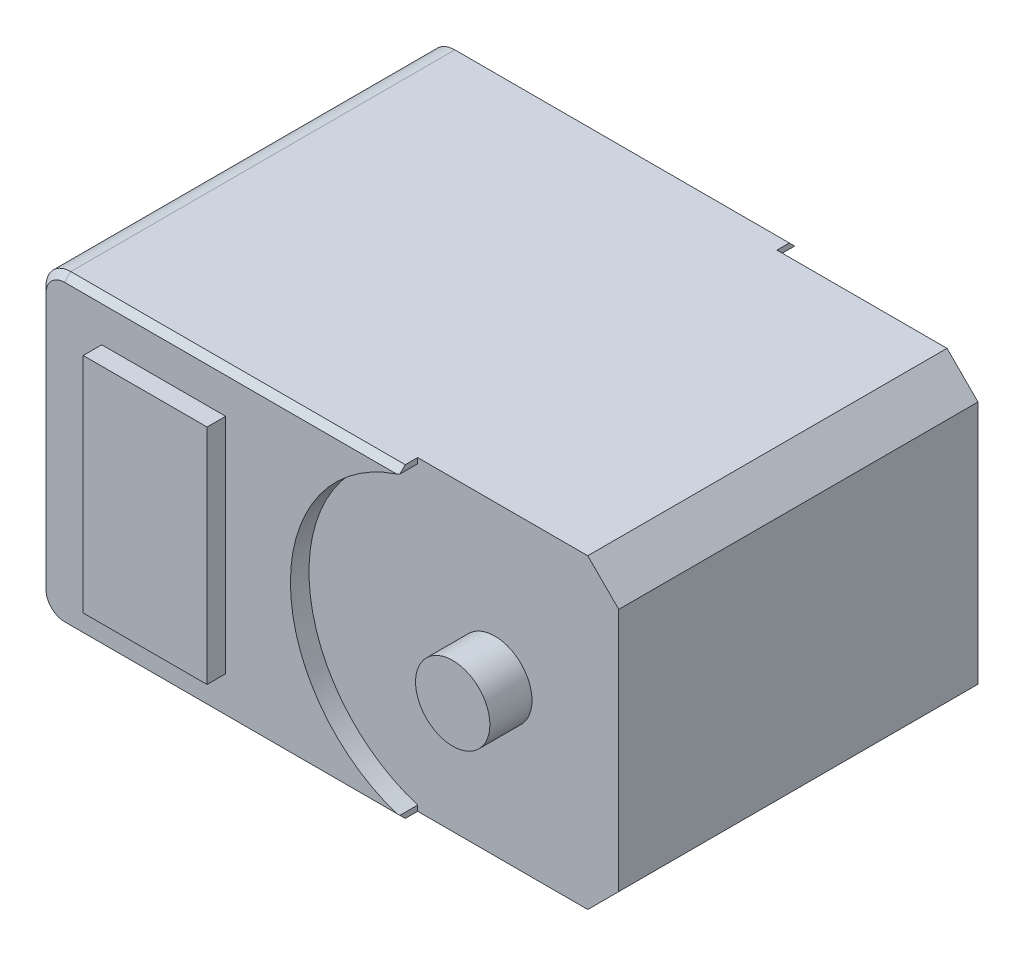
SolidWorks part; units mm, degrees
material "舵机材料"
ref_plane "前视基准面" through (0, 0, 0) normal (0, 0, 1) x (1, 0, 0)
ref_plane "上视基准面" through (0, 0, 0) normal (0, 1, 0) x (1, 0, 0)
ref_plane "右视基准面" through (0, 0, 0) normal (1, 0, 0) x (0, 0, -1)
other "Configuration Table"
sketch "草图1" plane through (0, 0, 0) normal (0, 0, 1) x (1, 0, 0)
  line L1 (0, 0) -> (45.23, 0)
  line L2 (0, 0) -> (0, 24.73)
  line L3 (0, 24.73) -> (45.23, 24.73)
  line L4 (45.23, 0) -> (45.23, 24.73)
  dimension "D1" = 45.23
  dimension "D2" = 24.73
extrude "凸台-拉伸1" add sketch "草图1" along normal blind 35
sketch "草图2" plane through (0, 0, 0) normal (0, 0, 1) x (1, 0, 0)
  line L1 (45.23, 24.73) -> (30.8978, 24.73)
  line L2 (45.23, 24.73) -> (45.23, 0)
  line L3 (45.23, 0) -> (30.8978, 0)
  line L9 (0, 24.73) -> (0, 0)
  line L10 (0, 0) -> (45.23, 0)
  line L11 (45.23, 0) -> (45.23, 24.73)
  line L12 (45.23, 24.73) -> (0, 24.73)
  line L14 (30.8978, 0) -> (45.23, 0)
  line L15 (45.23, 0) -> (45.23, 24.73)
  line L16 (45.23, 24.73) -> (30.8978, 24.73)
  arc A0 (30.8978, 24.73) -> (30.8978, 0) centre (32.73, 12.365) ccw
  dimension "D2" = 0
extrude "切除-拉伸1" cut sketch "草图2" along normal blind 3 contours L1 A0 L3 L2 region at (33.867, 12.365, 0)
sketch "草图5" plane through (0, 0, 0) normal (0, 0, 1) x (1, 0, 0)
  line L0 (30.8978, 24.73) -> (0, 24.73) construction
  line L2 (0, 0) -> (0, 24.73)
  line L4 (29, 0) -> (29, 24.73)
  line L5 (30.8978, 0) -> (30.8978, 24.73)
  line L14 (30.8978, 24.73) -> (0, 24.73)
  line L15 (0, 0) -> (30.8978, 0)
  line L16 (0, 24.73) -> (0, 0)
  line L17 (30.8978, 24.73) -> (29, 24.73)
  line L18 (29, 0) -> (30.8978, 0)
  line L19 (0, 24.73) -> (0, 0)
  arc A4 (30.8978, 24.73) -> (30.8978, 0) centre (32.73, 12.365) ccw
  dimension "D1" = 29
  dimension "D3" = 0
extrude "切除-拉伸3" cut sketch "草图5" along normal up to surface (3 mm away) contours L4 L18 L5 L17 region at (29.5901, 0.137, 0) region at (29.5901, 24.593, 0) region at (29.9546, 12.365, 0) up to face at (35.397, 12.365, 3)
ref_plane "基准面1" through (0, 0, 17.5) normal (0, 0, 1) x (1, 0, 0)
mirror "镜向1" about plane through (0, 0, 17.5) normal (0, 0, 1) of "切除-拉伸3", "切除-拉伸1"
sketch "草图3" plane through (0, 0, 0) normal (0, 0, 1) x (1, 0, 0)
  arc A0 (29, 24.2955) -> (29, 0.4345) centre (32.73, 12.365) ccw construction
  arc A1 (29, 24.2955) -> (29, 0.4345) centre (32.73, 12.365) ccw
  circle A3 centre (35.23, 12.365) radius 3
  dimension "D1" = 6
  dimension "D2" = 2.5
extrude "凸台-拉伸2" add sketch "草图3" along normal blind 17.9 and the other way blind 18.6 from surface contours A3 region at (35.23, 12.365, 0) starting at plane "基准面1"
sketch "草图4" plane through (0, 0, 0) normal (0, 0, 1) x (1, 0, 0)
  line L0 (0, 12.365) -> (51.1364, 12.365) construction
  line L1 (0, 24.73) -> (30.8978, 24.73)
  line L2 (0, 24.73) -> (0, 19.73)
  line L3 (0, 19.73) -> (30.8978, 19.73)
  line L4 (30.8978, 24.73) -> (30.8978, 19.73)
  line L5 (0, 24.73) -> (0, 0) construction
  line L6 (30.8978, 0) -> (30.8978, 5)
  line L7 (0, 0) -> (0, 5)
  line L8 (0, 0) -> (30.8978, 0)
  line L9 (0, 5) -> (30.8978, 5)
  dimension "D1" = 5
extrude "切除-拉伸2" cut sketch "草图4" along normal blind 1.5
chamfer "倒角1" distance 2.5 angle 45 2 edges at (45.23, 24.73, 17.5) (45.23, 0, 17.5)
fillet "圆角1" radius 2 2 edges at (0, 24.73, 18.25) (0, 0, 18.25)
sketch "草图6" plane through (0, 0, 35) normal (0, 0, 1) x (1, 0, 0)
  line L0 (-50.6859, 12.365) -> (-40.6859, 12.365) construction
  line L2 (0, 22.73) -> (0, 2) construction
  line L3 (5, 21.365) -> (15, 21.365)
  line L4 (5, 21.365) -> (5, 3.365)
  line L5 (5, 3.365) -> (15, 3.365)
  line L6 (15, 21.365) -> (15, 3.365)
  line L12 (29, 24.73) -> (2, 24.73)
  line L13 (0, 22.73) -> (0, 2)
  line L14 (2, 0) -> (29, 0)
  line L15 (29, 0) -> (29, 0.4345)
  line L16 (29, 24.2955) -> (29, 24.73)
  line L17 (29, 24.73) -> (2, 24.73)
  line L18 (0, 22.73) -> (0, 2)
  line L19 (2, 0) -> (29, 0)
  line L20 (29, 0) -> (29, 0.4345)
  line L21 (29, 24.2955) -> (29, 24.73)
  arc A3 (2, 24.73) -> (0, 22.73) centre (2, 22.73) ccw
  arc A5 (29, 24.2955) -> (29, 0.4345) centre (32.73, 12.365) ccw
  arc A8 (29, 24.2955) -> (29, 0.4345) centre (32.73, 12.365) ccw
  arc A9 (2, 24.73) -> (0, 22.73) centre (2, 22.73) ccw
  arc A10 (0, 2) -> (2, 0) centre (2, 2) ccw
  arc A11 (0, 2) -> (2, 0) centre (2, 2) ccw
  point P3 (-45.6859, 12.365)
  dimension "D1" = 9
  dimension "D2" = 0
  dimension "D3" = 5
  dimension "D4" = 10
extrude "切除-拉伸4" cut sketch "草图6" against normal blind 1.5
chamfer "倒角2" distance 0.5 angle 45 12 edges at (0, 21.23, 1.5) (0.5858, 24.1442, 1.5) (15.5, 24.73, 1.5) (0, 12.365, 0) (0, 3.5, 1.5) (0.5858, 0.5858, 1.5) (15.5, 0, 1.5) (15.5, 24.73, 33.5) (0.5858, 24.1442, 33.5) (0, 12.365, 33.5) (0.5858, 0.5858, 33.5) (15.5, 0, 33.5)
